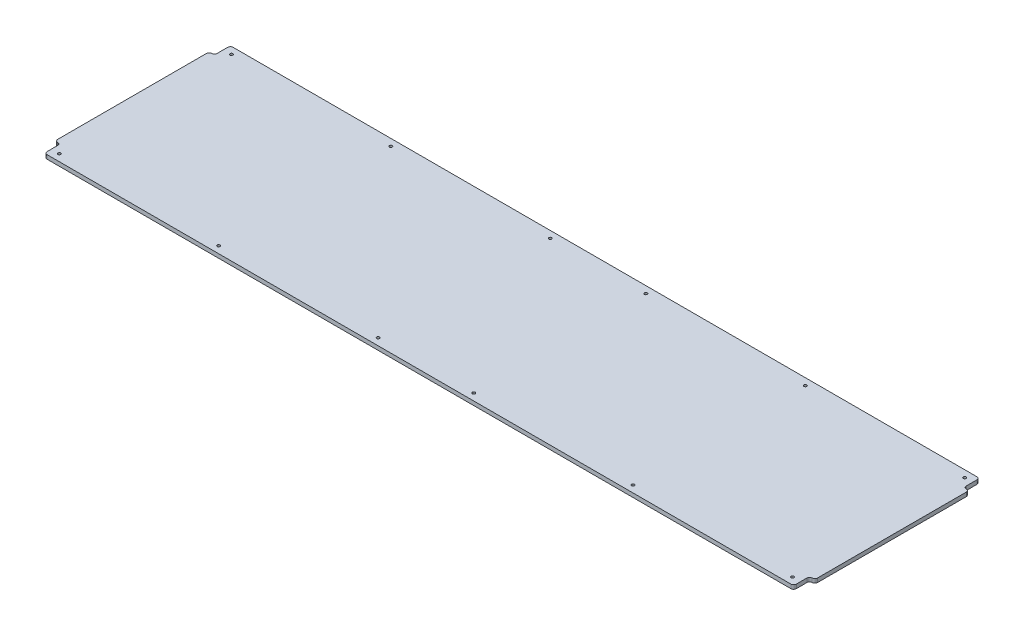
SolidWorks part; units mm, degrees
material "PE High Density"
ref_plane "Front Plane" through (0, 0, 0) normal (0, 0, 1) x (1, 0, 0)
ref_plane "Top Plane" through (0, 0, 0) normal (0, 1, 0) x (1, 0, 0)
ref_plane "Right Plane" through (0, 0, 0) normal (1, 0, 0) x (0, 0, -1)
sketch "Sketch1" plane through (0, 0, 0) normal (0, 1, 0) x (1, 0, 0)
  line L0 (-895.35, 222.25) -> (-895.35, 184.15)
  line L1 (-895.35, 222.25) -> (895.35, 222.25)
  line L2 (-908.05, 184.15) -> (-908.05, -184.15)
  line L3 (-895.35, -222.25) -> (895.35, -222.25)
  line L4 (908.05, 184.15) -> (908.05, -184.15)
  line L5 (-908.05, 222.25) -> (908.05, -222.25) construction
  line L6 (-908.05, -222.25) -> (908.05, 222.25) construction
  line L9 (908.05, -184.15) -> (895.35, -184.15)
  line L10 (895.35, -222.25) -> (895.35, -184.15)
  line L13 (908.05, 184.15) -> (895.35, 184.15)
  line L14 (895.35, 222.25) -> (895.35, 184.15)
  line L15 (-895.35, 184.15) -> (-908.05, 184.15)
  line L16 (-908.05, -184.15) -> (-895.35, -184.15)
  line L17 (-895.35, -184.15) -> (-895.35, -222.25)
  point P0 (0, 0)
  dimension "D1" = 1816.1
  dimension "D2" = 444.5
  dimension "D3" = 38.1
  dimension "D4" = 12.7
extrude "Boss-Extrude1" add sketch "Sketch1" along normal blind 9.525
hole_wizard "17/64 (0.26563) Diameter Hole1" positions "Sketch3" profile "Sketch4" hole size "17/64" standard "ANSI Inch" end condition through all
sketch "Sketch3" plane through (0, 9.525, 0) normal (0, 1, 0) x (1, 0, 0)
  line L1 (-895.35, -222.25) -> (895.35, -222.25) construction
  line L3 (-876.3, -205.74) -> (-876.3, -222.25) construction
  line L4 (-876.3, 205.74) -> (-876.3, 222.25) construction
  line L5 (895.35, 222.25) -> (-895.35, 222.25) construction
  line L8 (-876.3, -205.74) -> (-495.3, -205.74) construction
  line L9 (-495.3, -205.74) -> (-114.3, -205.74) construction
  line L12 (-876.3, 205.74) -> (-495.3, 205.74) construction
  line L13 (-495.3, 205.74) -> (-114.3, 205.74) construction
  line L15 (-908.05, 184.15) -> (-908.05, -184.15) construction
  line L16 (0, 222.25) -> (0, -222.25) construction
  line L18 (495.3, 205.74) -> (114.3, 205.74) construction
  line L19 (876.3, 205.74) -> (495.3, 205.74) construction
  line L20 (495.3, -205.74) -> (114.3, -205.74) construction
  line L21 (876.3, -205.74) -> (495.3, -205.74) construction
  line L22 (876.3, 205.74) -> (876.3, 222.25) construction
  line L23 (876.3, -205.74) -> (876.3, -222.25) construction
  point P0 (-876.3, -205.74)
  point P20 (-495.3, -205.74)
  point P26 (-876.3, 205.74)
  point P41 (-495.3, 205.74)
  point P51 (-114.3, 205.74)
  point P53 (-114.3, -205.74)
  point P86 (114.3, -205.74)
  point P87 (114.3, 205.74)
  point P88 (495.3, 205.74)
  point P89 (876.3, 205.74)
  point P90 (495.3, -205.74)
  point P91 (876.3, -205.74)
  dimension "D1" = 31.75
  dimension "D2" = 16.51
  dimension "D3" = 381
sketch "Sketch4" plane through (-876.3, 9.525, 205.74) normal (1, 0, 0) x (0, 0, 1)
  line L0 (0, 0) -> (0, 9.525)
  line L1 (0, 9.525) -> (3.3735, 9.525)
  line L2 (3.3735, 9.525) -> (3.3735, 0)
  line L5 (3.3735, 0) -> (0, 0)
  line L11 (0, -6.35) -> (0, 107.95) construction
  dimension "Thru Hole Dia." = 6.747
  dimension "Thru Hole Depth" = 9.525
fillet "Fillet1" radius 6.35 12 edges at (895.35, 4.7625, 222.25) (895.35, 4.7625, 184.15) (908.05, 4.7625, 184.15) (908.05, 4.7625, -184.15) (895.35, 4.7625, -184.15) (895.35, 4.7625, -222.25) (-908.05, 4.7625, -184.15) (-895.35, 4.7625, -184.15) (-895.35, 4.7625, -222.25) (-895.35, 4.7625, 222.25) (-895.35, 4.7625, 184.15) (-908.05, 4.7625, 184.15)
